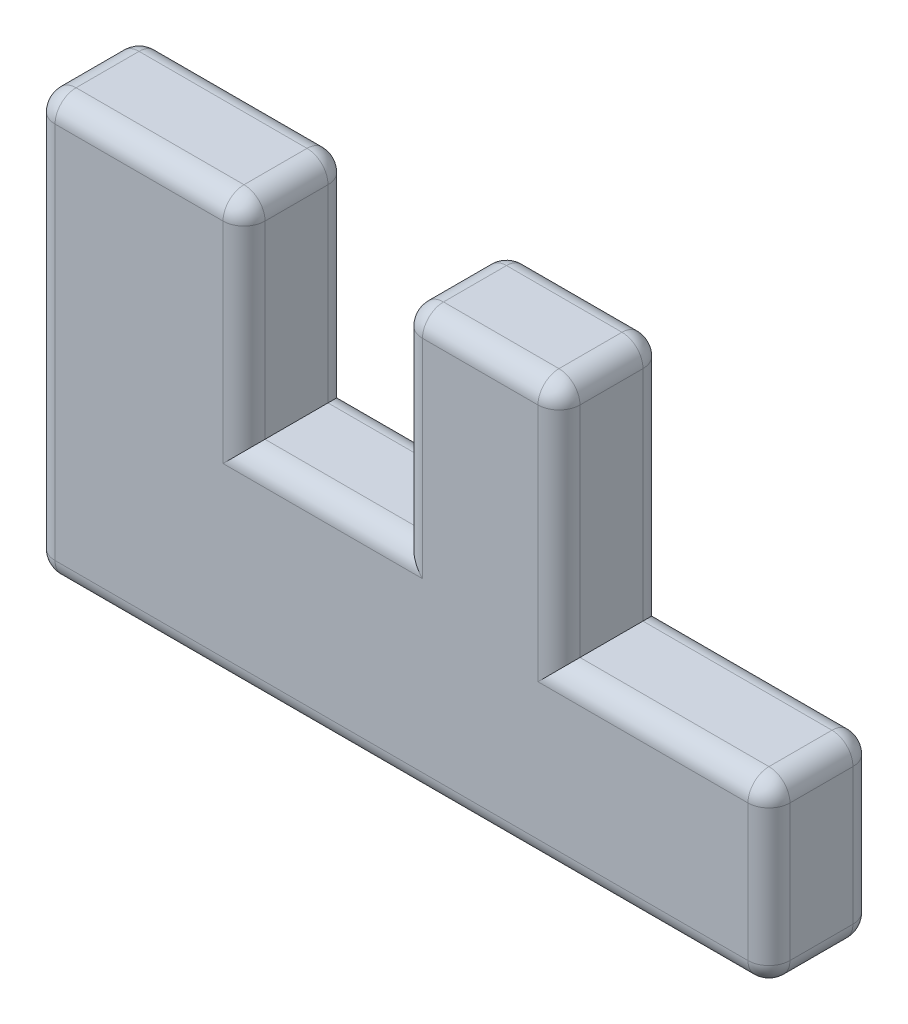
SolidWorks part; units mm, degrees
ref_plane "Front Plane" through (0, 0, 0) normal (0, 0, 1) x (1, 0, 0)
ref_plane "Top Plane" through (0, 0, 0) normal (0, 1, 0) x (1, 0, 0)
ref_plane "Right Plane" through (0, 0, 0) normal (1, 0, 0) x (0, 0, -1)
sketch "Sketch1" plane through (0, 0, 0) normal (0, 0, 1) x (1, 0, 0)
  line L0 (-33.3154, -51.4069) -> (55.5846, -51.4069)
  line L1 (55.5846, -51.4069) -> (55.5846, -29.8169)
  line L2 (55.5846, -29.8169) -> (30.1846, -29.8169)
  line L3 (30.1846, -29.8169) -> (30.1846, -0.8237)
  line L4 (30.1846, -0.8237) -> (11.1346, -0.8237)
  line L5 (11.1346, -0.8237) -> (11.1346, -26.0069)
  line L6 (11.1346, -26.0069) -> (-7.9154, -26.0069)
  line L7 (-7.9154, -26.0069) -> (-7.9154, -0.6069)
  line L8 (-7.9154, -0.6069) -> (-33.3154, -0.6069)
  line L9 (-33.3154, -0.6069) -> (-33.3154, -51.4069)
  dimension "D1" = 88.9
  dimension "D2" = 50.8
  dimension "D3" = 25.4
  dimension "D4" = 21.59
  dimension "D5" = 25.4
  dimension "D6" = 63.5
  dimension "D7" = 44.45
extrude "Boss-Extrude1" add sketch "Sketch1" along normal blind 12.7 contours L0 L1 L2 L3 L4 L5 L6 L7 L8 L9
fillet "Fillet1" radius 2.54 17 edges at (-20.6154, -0.6069, 0) (-33.3154, -26.0069, 0) (-33.3154, -26.0069, 12.7) (11.1346, -51.4069, 12.7) (11.1346, -51.4069, 0) (55.5846, -40.6119, 0) (42.8846, -29.8169, 0) (30.1846, -15.3203, 0) (20.6596, -0.8237, 0) (55.5846, -40.6119, 12.7) (42.8846, -29.8169, 12.7) (30.1846, -15.3203, 12.7) (11.1346, -13.4153, 12.7) (-7.9154, -13.3069, 12.7) (1.6096, -26.0069, 12.7) (20.6596, -0.8237, 12.7) (-20.6154, -0.6069, 12.7)
fillet "Fillet2" radius 2.54 9 edges at (-8.6593, -1.3508, 11.9561) (-7.9154, -0.6069, 6.35) (-7.9154, -1.3508, 0.7439) (11.8786, -1.5677, 11.9561) (11.1346, -0.8237, 6.35) (11.1346, -1.5677, 0.7439) (-7.9154, -14.5769, 0) (11.1346, -14.6853, 0) (1.6096, -26.0069, 0)
fillet "Fillet3" radius 2.54 15 edges at (-32.5714, -50.6629, 11.9561) (-32.5714, -50.6629, 0.7439) (-32.5714, -1.3508, 11.9561) (-32.5714, -1.3508, 0.7439) (29.4407, -1.5677, 11.9561) (29.4407, -1.5677, 0.7439) (54.8407, -50.6629, 11.9561) (54.8407, -50.6629, 0.7439) (54.8407, -30.5608, 11.9561) (54.8407, -30.5608, 0.7439) (-33.3154, -51.4069, 6.35) (-33.3154, -0.6069, 6.35) (30.1846, -0.8237, 6.35) (55.5846, -51.4069, 6.35) (55.5846, -29.8169, 6.35)
